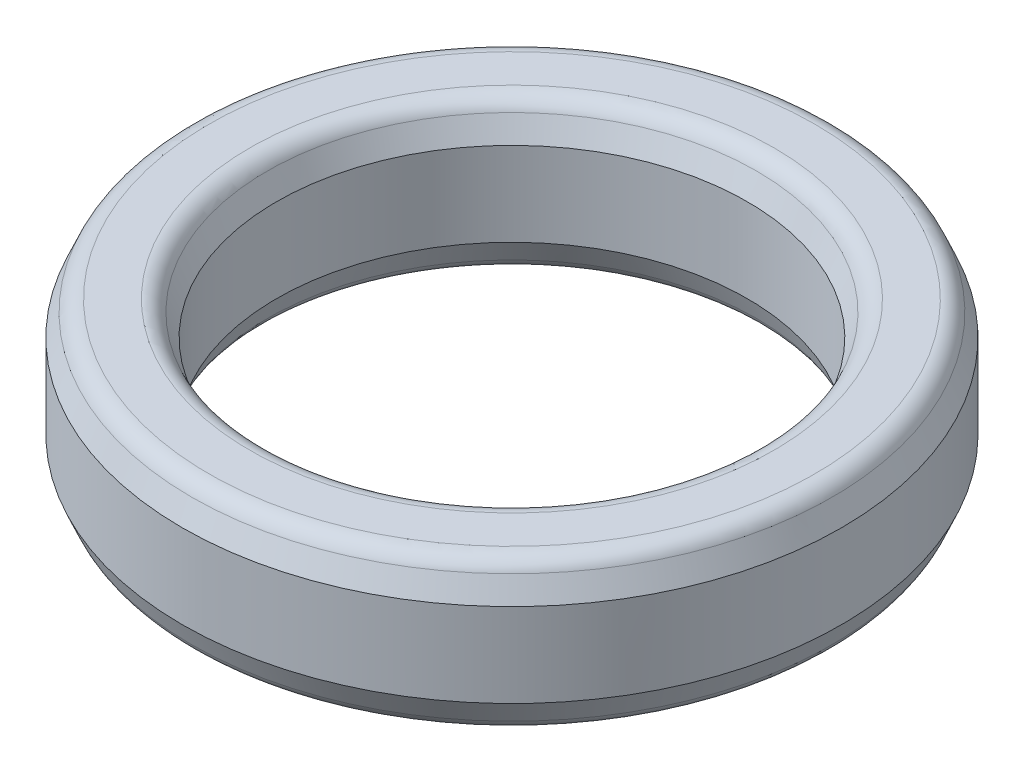
SolidWorks part; units mm, degrees
ref_plane "Front Plane" through (0, 0, 0) normal (0, 0, 1) x (1, 0, 0)
ref_plane "Top Plane" through (0, 0, 0) normal (0, 1, 0) x (1, 0, 0)
ref_plane "Right Plane" through (0, 0, 0) normal (1, 0, 0) x (0, 0, -1)
sketch "Gsk Profile" plane through (0, 0, 0) normal (0, 0, 1) x (1, 0, 0)
  line L0 (0, -6.35) -> (0, 6.35) construction
  line L1 (-3.9688, 0) -> (3.9688, 0) construction
  line L2 (-2.775, -6.35) -> (2.775, -6.35)
  line L3 (-2.775, 6.35) -> (2.775, 6.35)
  line L4 (-2.775, 6.35) -> (-3.9688, 3.5376)
  line L5 (2.775, 6.35) -> (3.9687, 3.5376)
  line L6 (-3.9688, -3.5376) -> (-2.775, -6.35)
  line L7 (2.775, -6.35) -> (3.9688, -3.5376)
  line L8 (-3.9688, 3.5376) -> (-3.9688, -3.5376)
  line L9 (3.9687, 3.5376) -> (3.9688, -3.5376)
  line L10 (-2.775, -6.35) -> (-3.9688, -3.5376)
  point P4 (0, 0)
  point P5 (0, 0)
  point P10 (0, 6.35)
  point P11 (0, -6.35)
  point P22 (-3.9688, 0)
  point P23 (3.9688, 0)
  dimension "Width_RTJ" = 7.9375
  dimension "Height_Of_Octagon" = 12.7
  dimension "D4" = 23
  dimension "D5" = 23
  dimension "D6" = 23
sketch "Pitch Diameter Point" plane through (0, 0, 0) normal (0, 1, 0) x (1, 0, 0)
  line L0 (0, 0) -> (47.625, 0) construction
  point P0 (47.625, 0)
  point P4 (23.8125, 0)
  dimension "Pitch_Diameter" = 47.625
ref_axis "Axis of Revolution" through (23.8125, 24.4422, 0) along (0, -1, 0)
revolve "Gasket Body" add sketch "Gsk Profile" angle 360 about axis through (23.8125, 24.4422, 0) along (0, -1, 0)
fillet "Gsk Corner Fillet" radius 1.5875 4 edges at (23.8125, -6.35, 26.5874) (23.8125, -6.35, 21.0376) (23.8125, 6.35, 21.0376) (23.8125, 6.35, 26.5874)
sketch3d "C&R Point Location"
  line L0 (23.8125, 3.5376, 0) -> (23.8125, 5.3828, 0) construction
  line L1 (23.8125, 5.3828, 0) -> (23.8125, 3.5376, 0) construction
  line L2 (23.8125, -5.3828, 0) -> (23.8125, -3.5376, 0) construction
  line L3 (23.8125, -6.35, 0) -> (23.8125, 6.35, 0) construction
  circle A0 centre (23.8125, 3.5376, 0) radius 19.8438 construction
  circle A1 centre (23.8125, -3.5376, 0) radius 19.8438 construction
  point P0 (23.8125, 6.35, 0)
  point P1 (23.8125, -6.35, 0)
  point P10 (23.8125, 0, 0)
  point P11 (23.8125, 3.5376, 0)
  point P12 (23.8125, -3.5376, 0)
  point P15 (23.8125, 23.3813, 0)
  point P19 (23.8125, 16.3062, 0)
other "CPoint1" parameters "Diameter"=31.75, "StubLength"=0
ref_axis "Axis2" through (23.8125, 13.5376, 0) along (0, -1, 0)
other "RPoint1"
other "CPoint2" parameters "Diameter"=31.75, "StubLength"=0
ref_axis "Axis3" through (23.8125, -13.5376, 0) along (0, 1, 0)
